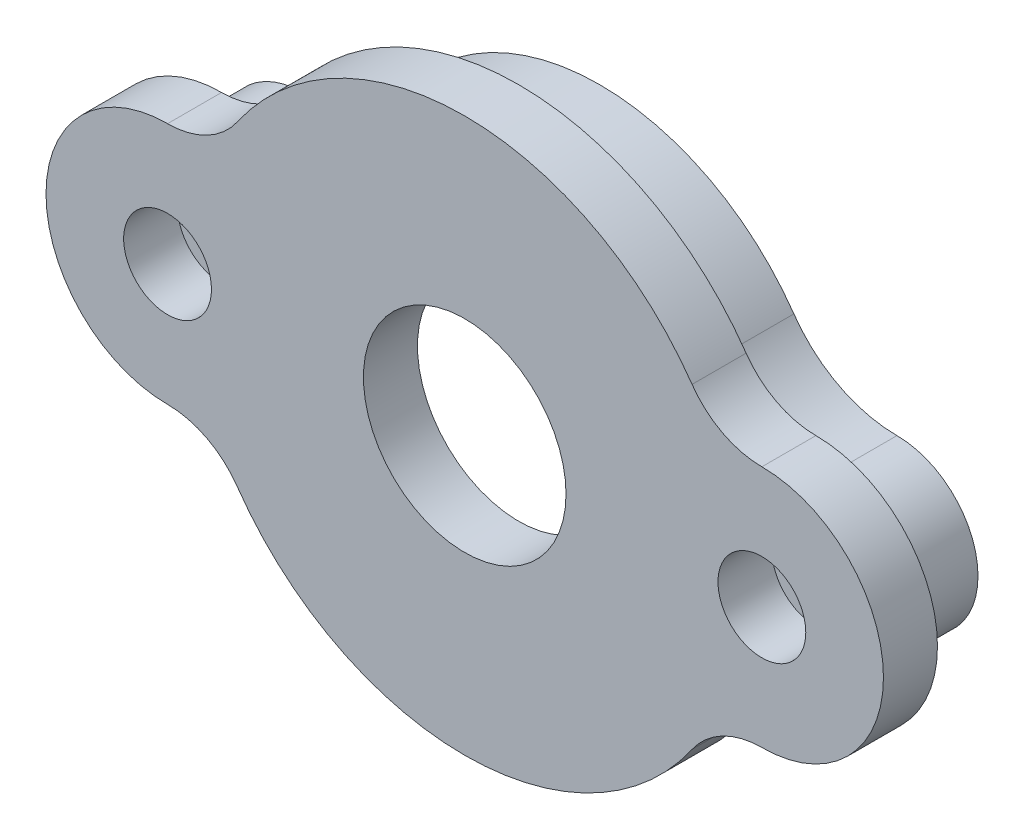
SolidWorks part; units mm, degrees
material "Plain Carbon Steel"
ref_plane "Ön Düzlem" through (0, 0, 0) normal (0, 0, 1) x (1, 0, 0)
ref_plane "Üst Düzlem" through (0, 0, 0) normal (0, 1, 0) x (1, 0, 0)
ref_plane "Sağ Düzlem" through (0, 0, 0) normal (1, 0, 0) x (0, 0, -1)
sketch "Sketch1" plane through (0, 0, 0) normal (0, 0, 1) x (1, 0, 0)
  circle A0 centre (0, 0) radius 16
  circle A1 centre (0, 0) radius 7.5
  arc A2 (-22, 6) -> (-22, -6) centre (-22, 0) ccw
  arc A3 (22, -6) -> (22, 6) centre (22, 0) ccw
  arc A4 (-22, 6) -> (-14.3692, 9.9888) centre (-22, 15.2935) ccw
  arc A5 (22, 6) -> (14.3692, 9.9888) centre (22, 15.2935) cw
  arc A6 (-22, -6) -> (-14.3692, -9.9888) centre (-22, -15.2935) cw
  arc A7 (22, -6) -> (14.3692, -9.9888) centre (22, -15.2935) ccw
  arc A8 (-14.3692, 9.9888) -> (14.3692, 9.9888) centre (0, 0) cw
  arc A9 (-14.3692, -9.9888) -> (14.3692, -9.9888) centre (0, 0) ccw
  arc A10 (-22, 9) -> (-22, -9) centre (-22, 0) ccw
  arc A11 (-22, -9) -> (-16.8325, -11.7012) centre (-22, -15.2935) cw
  arc A12 (-16.8325, -11.7012) -> (16.8325, -11.7012) centre (0, 0) ccw
  arc A13 (22, -9) -> (16.8325, -11.7012) centre (22, -15.2935) ccw
  arc A14 (22, -9) -> (22, 9) centre (22, 0) ccw
  arc A15 (22, 9) -> (16.8325, 11.7012) centre (22, 15.2935) cw
  arc A16 (-16.8325, 11.7012) -> (16.8325, 11.7012) centre (0, 0) cw
  arc A17 (-22, 9) -> (-16.8325, 11.7012) centre (-22, 15.2935) ccw
  dimension "D1" = 32
  dimension "D2" = 15
  dimension "D3" = 1.5
  dimension "D4" = 1.5
  dimension "D7" = 6
  dimension "D8" = 6
  dimension "D5" = 22
  dimension "D6" = 22
  dimension "D9" = 3
extrude "Boss-Extrude1" add sketch "Sketch1" along normal blind 10 contours A17 A10 A11 A12 A13 A14 A15 A16 A9 A6 A2 A4 A8 A5 A3 A7 | A6 A9 A7 A3 A5 A8 A4 A2 A0 | A0 A1 | A1 region at (-15.5475, 0, 0) region at (0, 0, 0) region at (-17.3888, 6.4721, 0) region at (-18.7402, 9.0573, 0)
extrude "Cut-Extrude1" cut sketch "Sketch1<3>" along normal blind 6 contours A0 A1 region at (-15.5475, 0, 0)
sketch "Sketch1<3>" plane through (0, 0, 0) normal (0, 0, 1) x (1, 0, 0) same geometry as "Sketch1"
extrude "Cut-Extrude2" cut sketch "Sketch1<4>" along normal blind 10 contours A1 region at (0, 0, 0)
sketch "Sketch1<4>" plane through (0, 0, 0) normal (0, 0, 1) x (1, 0, 0) same geometry as "Sketch1"
extrude "Cut-Extrude3" cut sketch "Sketch1<5>" along normal blind 6 contours A17 A10 A11 A12 A13 A14 A15 A16 A9 A6 A2 A4 A8 A5 A3 A7 region at (-18.7402, 9.0573, 0)
sketch "Sketch1<5>" plane through (0, 0, 0) normal (0, 0, 1) x (1, 0, 0) same geometry as "Sketch1"
sketch "Sketch3" plane through (0, 0, 10) normal (0, 0, 1) x (1, 0, 0)
  circle A0 centre (22, 0) radius 1.75
  circle A1 centre (-22, 0) radius 1.75
  dimension "D1" = 3.5
  dimension "D2" = 3.5
extrude "Cut-Extrude4" cut sketch "Sketch3" against normal blind 10
sketch "Sketch4" plane through (0, 0, 10) normal (0, 0, 1) x (1, 0, 0)
  circle A0 centre (22, 0) radius 3.25
  circle A1 centre (-22, 0) radius 3.25
  dimension "D1" = 6.5
  dimension "D2" = 6.5
extrude "Cut-Extrude5" cut sketch "Sketch4" against normal blind 4
